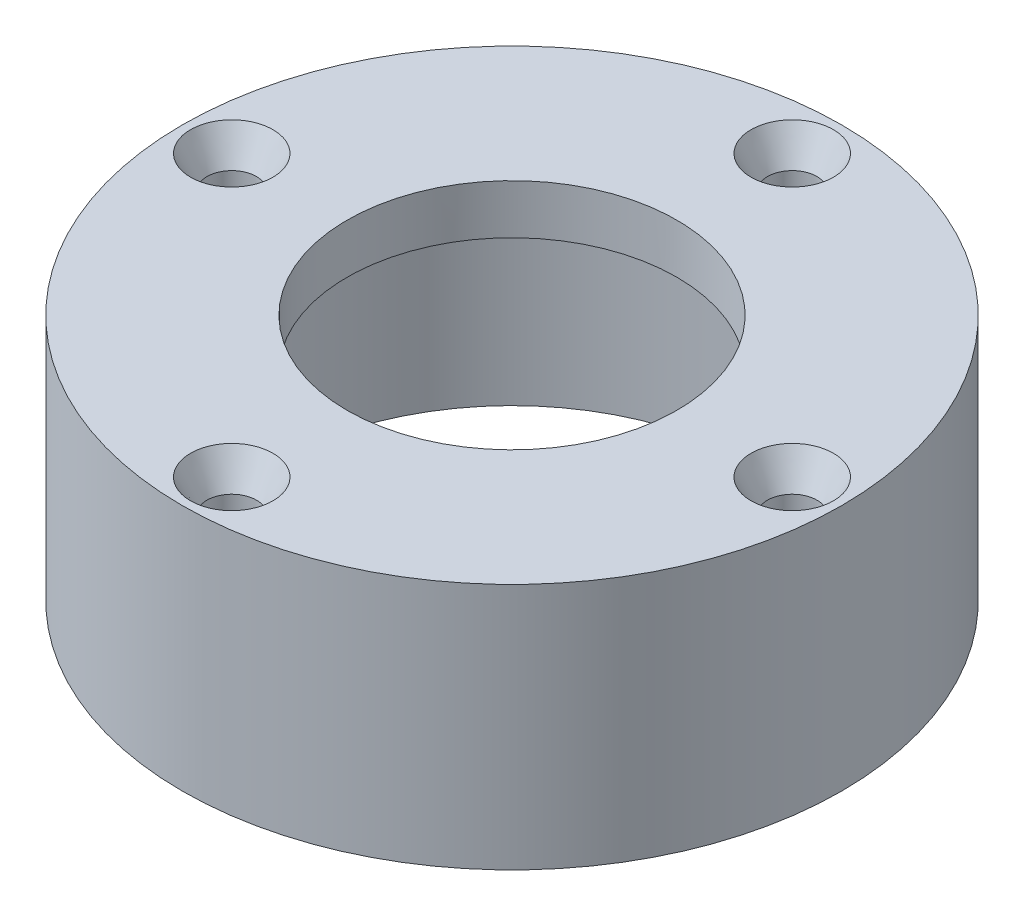
SolidWorks part; units mm, degrees
ref_plane "Front Plane" through (0, 0, 0) normal (0, 0, 1) x (1, 0, 0)
ref_plane "Top Plane" through (0, 0, 0) normal (0, 1, 0) x (1, 0, 0)
ref_plane "Right Plane" through (0, 0, 0) normal (1, 0, 0) x (0, 0, -1)
sketch "Sketch1" plane through (0, 0, 0) normal (0, 1, 0) x (1, 0, 0)
  circle A0 centre (0, 0) radius 20
extrude "Boss-Extrude1" add sketch "Sketch1" along normal blind 15
sketch "Sketch4" plane through (0, 0, 0) normal (0, -1, 0) x (1, 0, 0)
  circle A0 centre (0, 0) radius 14.5
extrude "Cut-Extrude3" cut sketch "Sketch4" against normal blind 12
sketch "Sketch5" plane through (0, 15, 0) normal (0, 1, 0) x (1, 0, 0)
  circle A0 centre (0, 0) radius 10
extrude "Cut-Extrude4" cut sketch "Sketch5" against normal blind 12
sketch "Sketch6" plane through (0, 15, 0) normal (0, 1, 0) x (1, 0, 0)
  line L0 (0, 0) -> (0, 28.6341) construction
  line L1 (0, 0) -> (42.7374, 0) construction
  circle A0 centre (0, 17) radius 1.5
  circle A1 centre (17, 0) radius 1.5
  circle A2 centre (0, -17) radius 1.5
  circle A3 centre (-17, 0) radius 1.5
  point P18 (0, 0)
  dimension "D1" = 17
extrude "Cut-Extrude5" cut sketch "Sketch6" against normal through all
sketch "Sketch7" plane through (0, 15, 0) normal (0, 1, 0) x (1, 0, 0)
  circle A0 centre (0, 17) radius 2.5
  circle A1 centre (17, 0) radius 2.5
  circle A2 centre (0, -17) radius 2.5
  circle A3 centre (-17, 0) radius 2.5
  point P12 (0, 0)
  dimension "D1" = 4
extrude "Cut-Extrude7" cut sketch "Sketch7" against normal blind 2 draft 27
